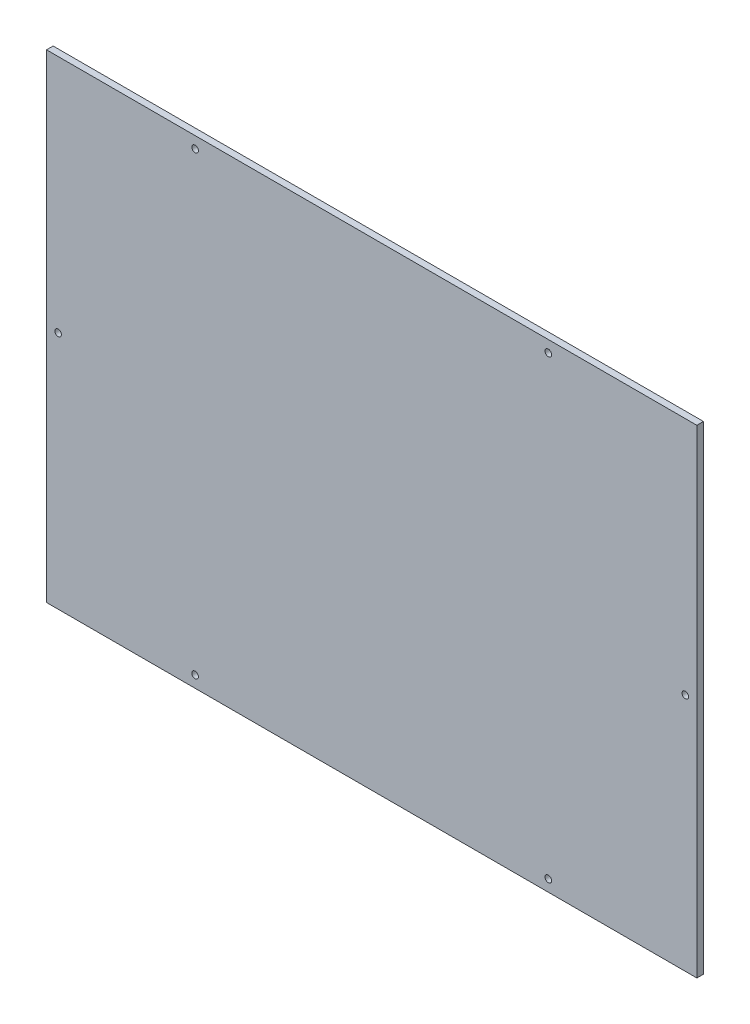
SolidWorks part; units mm, degrees
ref_plane "Piano frontale" through (0, 0, 0) normal (0, 0, 1) x (1, 0, 0)
ref_plane "Piano superiore" through (0, 0, 0) normal (0, 1, 0) x (1, 0, 0)
ref_plane "Piano destro" through (0, 0, 0) normal (1, 0, 0) x (0, 0, -1)
sketch "Schizzo1" plane through (0, 0, 0) normal (0, 0, 1) x (1, 0, 0)
  line L0 (-197, 351.6275) -> (-197, -66.2585) construction
  line L1 (0, 0) -> (-394, 0)
  line L2 (0, 0) -> (0, 290)
  line L3 (0, 290) -> (-394, 290)
  line L4 (-394, 0) -> (-394, 290)
  line L5 (-387.9788, 145) -> (120.8821, 145) construction
  circle A0 centre (-90, 283) radius 2
  circle A1 centre (-7, 145) radius 2
  circle A2 centre (-304, 283) radius 2
  circle A3 centre (-387, 145) radius 2
  circle A4 centre (-304, 7) radius 2
  circle A7 centre (-90, 7) radius 2
  point P9 (-197, 145)
  dimension "D3" = 4
  dimension "D1" = 394
  dimension "314" = 290
  dimension "D4" = 7
  dimension "D5" = 90
  dimension "D6" = 7
extrude "Estrusione-Estrusione1" add sketch "Schizzo1" along normal blind 4
